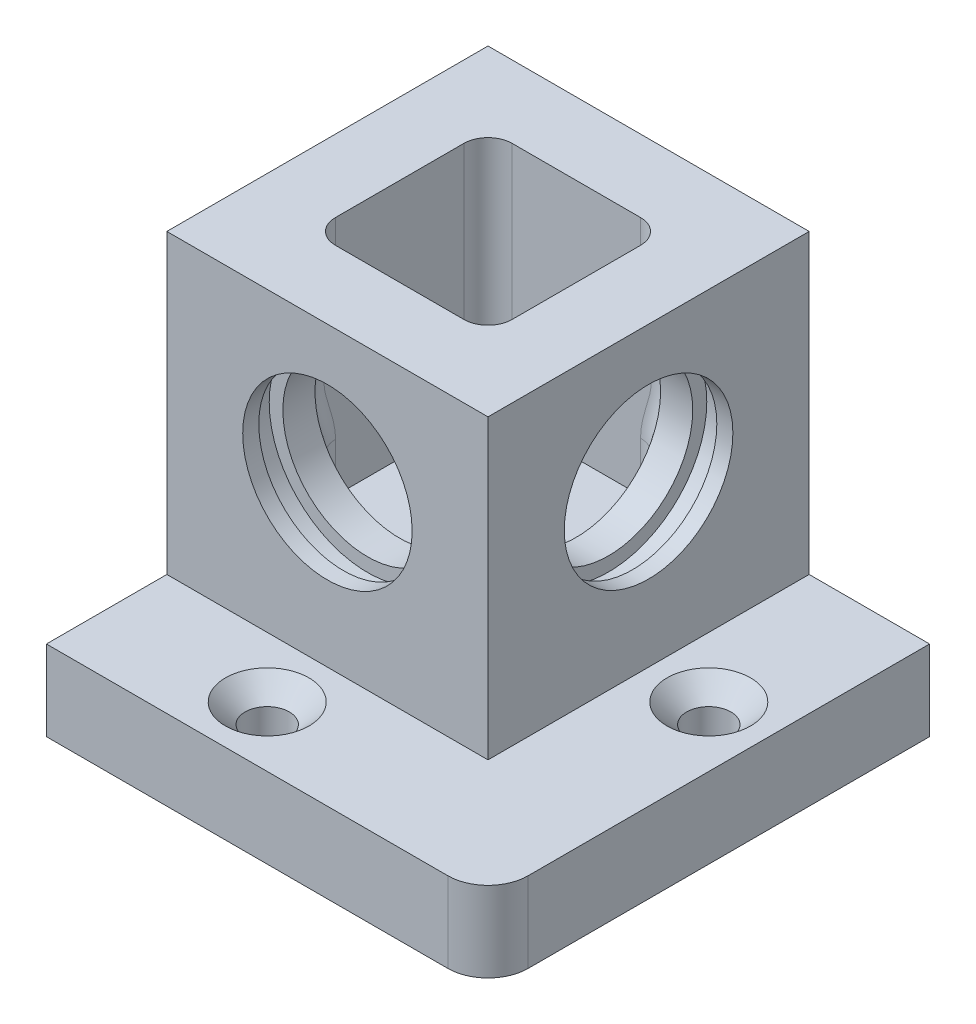
SolidWorks part; units mm, degrees
material "Acrylic (Medium-high impact)"
ref_plane "Front Plane" through (0, 0, 0) normal (0, 0, 1) x (1, 0, 0)
ref_plane "Top Plane" through (0, 0, 0) normal (0, 1, 0) x (1, 0, 0)
ref_plane "Right Plane" through (0, 0, 0) normal (1, 0, 0) x (0, 0, -1)
sketch "Sketch1" plane through (0, 0, 0) normal (0, 1, 0) x (1, 0, 0)
  line L1 (-27.5, -27.5) -> (27.5, -27.5)
  line L2 (-27.5, -27.5) -> (-27.5, 27.5)
  line L3 (-27.5, 27.5) -> (27.5, 27.5)
  line L4 (27.5, -27.5) -> (27.5, 27.5)
  line L5 (-27.5, -27.5) -> (27.5, 27.5) construction
  line L6 (-27.5, 27.5) -> (27.5, -27.5) construction
  point P0 (0, 0)
  dimension "D1" = 55
  dimension "D2" = 55
extrude "Base" add sketch "Sketch1" along normal blind 47
sketch "Sketch2" plane through (0, 47, 0) normal (0, 1, 0) x (1, 0, 0)
  line L0 (-27.5, -12.5) -> (12.5, -12.5)
  line L1 (-27.5, 27.5) -> (-27.5, -27.5) construction
  line L2 (12.5, -12.5) -> (12.5, 27.5)
  line L3 (27.5, 27.5) -> (-27.5, 27.5) construction
  line L4 (12.5, 27.5) -> (27.5, 27.5)
  line L5 (27.5, 27.5) -> (27.5, -27.5)
  line L6 (27.5, -27.5) -> (-27.5, -27.5)
  line L7 (-27.5, -27.5) -> (-27.5, -12.5)
  dimension "D1" = 15
  dimension "D2" = 15
extrude "ChamberHousing" cut sketch "Sketch2" against normal offset from surface (37 mm away) 10 up to face at (0, 0, 0)
sketch "Sketch3" plane through (0, 47, 0) normal (0, 1, 0) x (1, 0, 0)
  line L0 (-27.5, 27.5) -> (-27.5, -12.5) construction
  line L1 (-18.5, 18.5) -> (3.5, 18.5)
  line L2 (-18.5, 18.5) -> (-18.5, -3.5)
  line L3 (-18.5, -3.5) -> (3.5, -3.5)
  line L4 (3.5, 18.5) -> (3.5, -3.5)
  line L5 (-18.5, 18.5) -> (3.5, -3.5) construction
  line L6 (-18.5, -3.5) -> (3.5, 18.5) construction
  line L8 (12.5, -12.5) -> (-27.5, -12.5) construction
  point P0 (-7.5, 7.5)
  point P5 (-27.5, 7.5)
  dimension "D1" = 22
  dimension "D2" = 22
  dimension "D3" = 9
  dimension "D4" = 9
extrude "Chamber" cut sketch "Sketch3" against normal blind 30
sketch "Sketch4" plane through (0, 0, 12.5) normal (0, 0, 1) x (1, 0, 0)
  line L2 (-27.5, 10) -> (-27.5, 47) construction
  line L4 (12.5, 10) -> (12.5, 47) construction
  line L7 (12.5, 47) -> (-27.5, 47) construction
  circle A0 centre (-7.5, 29.95) radius 10.55
  dimension "D1" = 9.45
  dimension "D2" = 9.45
  dimension "D3" = 6.5
extrude "Cut-Extrude3" cut sketch "Sketch4" against normal up to next
ref_plane "Plane1" through (0, 0, 10.5) normal (0, 0, 1) x (1, 0, 0)
sketch "Sketch6" plane through (0, 0, 10.5) normal (0, 0, 1) x (1, 0, 0)
  circle A0 centre (-7.5, 29.95) radius 12.25
  dimension "D1" = 24.5
extrude "o-Ring" cut sketch "Sketch6" against normal blind 3
sketch "Sketch7" plane through (12.5, 0, 0) normal (1, 0, 0) x (0, 0, -1)
  line L2 (27.5, 47) -> (-12.5, 47) construction
  line L4 (-12.5, 10) -> (-12.5, 47) construction
  line L7 (27.5, 10) -> (27.5, 47) construction
  circle A0 centre (7.5, 30) radius 10.5
  dimension "D1" = 6.5
  dimension "D2" = 9.5
  dimension "D3" = 9.5
extrude "Cut-Extrude5" cut sketch "Sketch7" against normal up to next
ref_plane "Plane2" through (10.5, 0, 0) normal (1, 0, 0) x (0, 0, -1)
sketch "Sketch8" plane through (10.5, 0, 0) normal (1, 0, 0) x (0, 0, -1)
  circle A0 centre (7.5, 30) radius 12.25
  dimension "D1" = 24.5
extrude "Cut-Extrude6" cut sketch "Sketch8" against normal blind 3
fillet "Fillet1" radius 5 1 edges at (27.5, 5, 27.5)
hole_wizard "CSK for M5 Countersunk Flat Head Screw1" positions "Sketch10" profile "Sketch9" countersink size "M5" standard "DIN" end condition through all
sketch "Sketch10" plane through (0, 10, 0) normal (0, 1, 0) x (-1, 0, 0)
  line L0 (27.5, 12.5) -> (27.5, 27.5) construction
  line L1 (27.5, 27.5) -> (-22.5, 27.5) construction
  line L2 (-27.5, -27.5) -> (-12.5, -27.5) construction
  line L3 (-27.5, 22.5) -> (-27.5, -27.5) construction
  point P0 (-20, -7.5)
  point P1 (7.5, 20)
  point P6 (27.5, 20)
  dimension "D1" = 20
  dimension "D2" = 7.5
  dimension "D3" = 20
  dimension "D4" = 7.5
sketch "Sketch9" plane through (20, 10, -7.5) normal (1, 0, 0) x (0, 0, 1)
  line L0 (0, 0) -> (0, 10)
  line L1 (0, 10) -> (2.75, 10)
  line L2 (2.75, 10) -> (2.75, 2.45)
  line L3 (2.75, 2.45) -> (5.2, 0)
  line L5 (5.2, 0) -> (0, 0)
  line L6 (-2.75, 2.45) -> (-5.2, 0) construction
  line L11 (0, -6.35) -> (0, 107.95) construction
  dimension "Thru Hole Dia." = 5.5
  dimension "Thru Hole Depth" = 10
  dimension "Near C'Sink Dia." = 10.4
  dimension "Near C'Sink Angle" = 90
fillet "Fillet2" radius 3 4 edges at (3.5, 32, 3.5) (3.5, 32, -18.5) (-18.5, 32, -18.5) (-18.5, 32, 3.5)
